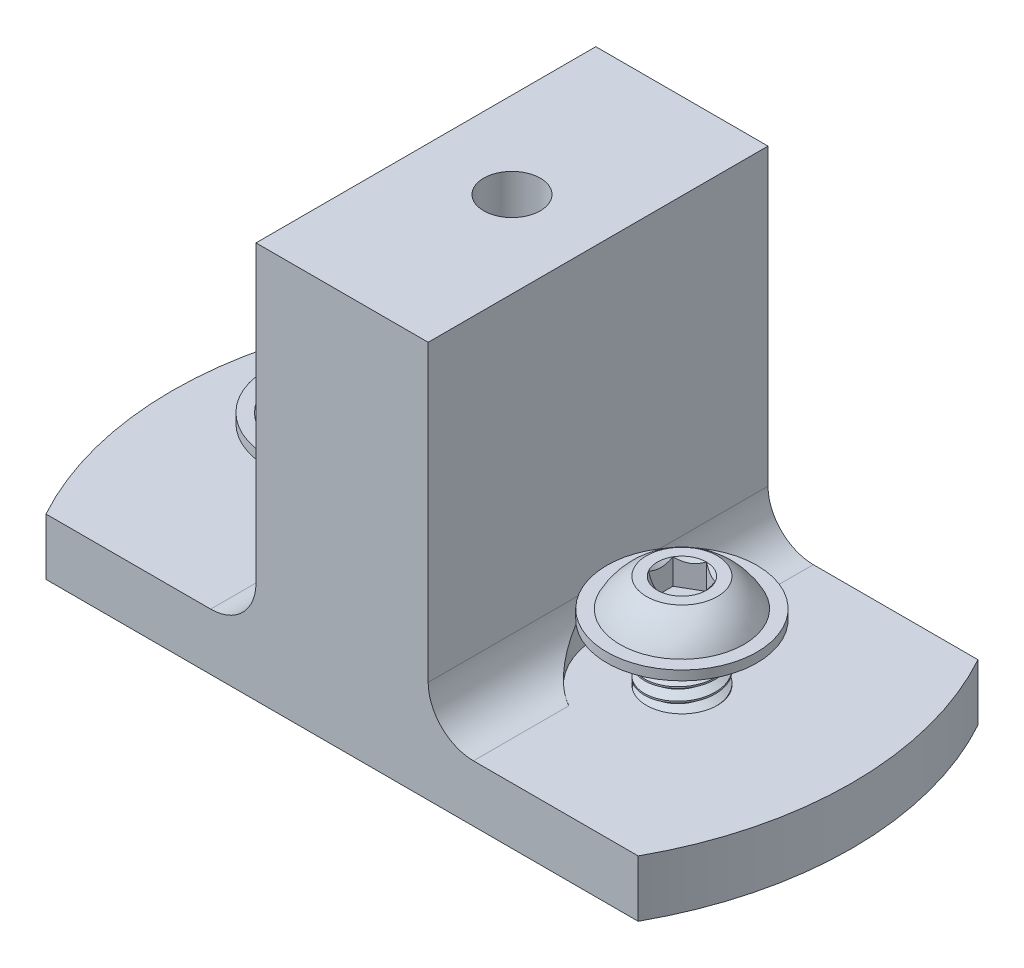
SolidWorks part; units mm, degrees
ref_plane "Front Plane" through (0, 0, 0) normal (0, 0, 1) x (1, 0, 0)
ref_plane "Top Plane" through (0, 0, 0) normal (0, 1, 0) x (1, 0, 0)
ref_plane "Right Plane" through (0, 0, 0) normal (1, 0, 0) x (0, 0, -1)
sketch "Sketch1" plane through (0, 0, 0) normal (0, 1, 0) x (1, 0, 0)
  line L0 (-19.05, 0) -> (19.05, 0) construction
  circle A0 centre (-19.05, 0) radius 3.9688
  point P3 (-23.0188, 0)
  point P4 (-15.0813, 0)
  dimension "D1" = 7.9375
  dimension "D2" = 38.1
extrude "Boss-Extrude1" add sketch "Sketch1" against normal blind 17.4625
sketch "Sketch2" plane through (0, -17.4625, 0) normal (0, -1, 0) x (1, 0, 0)
  circle A1 centre (-19.05, 0) radius 3.9688
  circle A2 centre (-19.05, 0) radius 3.9688
  point P0 (-19.05, -3.9688)
  dimension "D1" = 0
curve "Helix/Spiral1" pitch 1.4111 height 18.8736 turns 13.375
ref_plane "Plane1" through (-19.05, 0, 0) normal (1, 0, 0) x (0, 0, -1)
sketch "Sketch3" plane through (-19.05, 0, 0) normal (1, 0, 0) x (0, 0, -1)
  line L0 (4.1215, -17.3743) -> (2.8994, -18.0799) construction
  line L1 (2.8994, -18.0799) -> (4.1215, -18.7854) construction
  line L2 (4.1215, -18.7854) -> (4.1215, -17.3743) construction
  line L3 (3.0522, -17.9917) -> (3.0522, -18.1681) construction
  line L4 (3.9688, -17.4625) -> (3.9688, -18.6972) construction
  line L5 (2.8994, -18.0799) -> (3.0522, -18.0799) construction
  line L6 (3.9688, -18.0799) -> (4.1215, -18.0799) construction
  line L8 (2.8994, -18.0799) -> (-3.9688, -18.0799) construction
  line L9 (3.0522, -17.9917) -> (4.0451, -17.4184)
  line L10 (3.0522, -17.9917) -> (3.0522, -18.1681)
  line L11 (3.0522, -18.1681) -> (4.0451, -18.7413)
  line L12 (4.0451, -18.7413) -> (4.0451, -17.4184)
  line L14 (-3.9688, -18.0799) -> (-3.9688, -16.6687) construction
  line L15 (-3.9688, -16.6687) -> (-3.9688, -15.2576) construction
  line L16 (-3.9688, -15.2576) -> (-3.9687, -13.8465) construction
  line L17 (-3.9687, -13.8465) -> (-3.9688, -12.4354) construction
  line L18 (-3.9688, 0) -> (-3.9688, -17.4625) construction
  point P15 (4.0451, -18.0799)
  dimension "D1" = 1.4111
  dimension "D2" = 0.1764
sweep "Cut-Sweep1" cut profiles "Sketch3" path "Helix/Spiral1" align with end faces yes
sketch "Sketch4" plane through (0, -17.4625, 0) normal (0, -1, 0) x (1, 0, 0)
  circle A0 centre (-19.05, 0) radius 2.8994
extrude "Cut-Extrude1" cut sketch "Sketch4" against normal blind 1.4111 draft 45 flip side to cut
sketch "Sketch5" plane through (0, 0, 0) normal (0, 0, 1) x (1, 0, 0)
  line L0 (-19.05, 0) -> (-19.05, 4.2164)
  line L1 (-27.4701, 0) -> (-19.05, 0)
  line L2 (-19.05, 4.2164) -> (-23.0188, 4.2164)
  line L3 (-25.9969, 1.0541) -> (-27.4701, 1.0541)
  line L4 (-27.4701, 1.0541) -> (-27.4701, 0)
  line L5 (-19.05, 0) -> (-19.05, -17.4625) construction
  arc A0 (-23.0188, 4.2164) -> (-25.9969, 1.0541) centre (-19.05, -2.5047) ccw
  dimension "D1" = 4.2164
  dimension "D2" = 1.0541
  dimension "D3" = 16.8402
  dimension "D4" = 13.8938
revolve "Revolve1" add sketch "Sketch5" angle 360 mid plane about L0
sketch "Sketch6" plane through (0, 4.2164, 0) normal (0, 1, 0) x (1, 0, 0)
  line L1 (-19.05, 2.7496) -> (-21.4313, 1.3748)
  line L2 (-21.4313, 1.3748) -> (-21.4312, -1.3748)
  line L3 (-21.4312, -1.3748) -> (-19.05, -2.7496)
  line L4 (-19.05, -2.7496) -> (-16.6688, -1.3748)
  line L5 (-16.6688, -1.3748) -> (-16.6688, 1.3748)
  line L6 (-16.6688, 1.3748) -> (-19.05, 2.7496)
  circle A0 centre (-19.05, 0) radius 2.3813 construction
  dimension "D1" = 4.7625
extrude "Cut-Extrude2" cut sketch "Sketch6" against normal blind 2.8575
sketch "Sketch7" plane through (0, 4.2164, 0) normal (0, 1, 0) x (1, 0, 0)
  circle A0 centre (-19.05, 0) radius 2.7496
extrude "Cut-Extrude3" cut sketch "Sketch7" against normal blind 2.8575 draft 45
move or copy body "Body-Move/Copy1" bodies to move or copy 110 copy yes number of copies 1 translate (38.1, 0, 0)
sketch "Sketch8" plane through (0, 0, 0) normal (0, 1, 0) x (1, 0, 0)
  line L0 (-38.1, 0) -> (38.1, 0) construction
  line L2 (-33.1956, 19.05) -> (33.1956, 19.05)
  line L3 (-33.1956, -19.05) -> (33.1956, -19.05)
  line L4 (-38.1, 19.05) -> (38.1, 19.05) construction
  line L5 (-38.1, 19.05) -> (-38.1, -19.05) construction
  line L6 (-38.1, -19.05) -> (38.1, -19.05) construction
  line L7 (38.1, 19.05) -> (38.1, -19.05) construction
  arc A0 (-33.1956, 19.05) -> (-33.1956, -19.05) centre (1.3498, 0) ccw
  arc A1 (33.1956, 19.05) -> (33.1956, -19.05) centre (-1.3498, 0) cw
  circle A2 centre (19.05, 0) radius 3.9688
  circle A3 centre (-19.05, 0) radius 3.9688
  circle A4 centre (-19.05, 0) radius 3.9688
  dimension "D2" = 76.2
  dimension "D3" = 38.1
  dimension "D4" = 19.05
  dimension "D1" = 0
extrude "Boss-Extrude2" add sketch "Sketch8" against normal blind 6.35 from offset 6.35 separate body offset against normal yes
sketch "Sketch15" plane through (0, -6.35, 0) normal (0, 1, 0) x (1, 0, 0)
  line L0 (-10.6299, 0) -> (-10.6299, 19.05) construction
  line L1 (33.1956, 19.05) -> (-33.1956, 19.05) construction
  line L2 (10.6299, 0) -> (10.6299, 19.05) construction
  line L3 (0, 19.05) -> (-9.652, 19.05)
  line L4 (-9.652, 19.05) -> (-9.652, -19.05)
  line L5 (-33.1956, -19.05) -> (33.1956, -19.05) construction
  line L6 (0, 19.05) -> (9.652, 19.05)
  line L7 (9.652, 19.05) -> (9.652, -19.05)
  line L8 (9.652, -19.05) -> (-9.652, -19.05)
  circle A0 centre (-19.05, 0) radius 8.4201 construction
  circle A1 centre (19.05, 0) radius 8.4201 construction
  dimension "D1" = 19.304
extrude "Boss-Extrude7" add sketch "Sketch15" along normal blind 38.1
sketch "Sketch16" plane through (0, 31.75, 0) normal (0, 1, 0) x (1, 0, 0)
  circle A0 centre (0, 0) radius 3.175
extrude "Cut-Extrude5" cut sketch "Sketch16" against normal through all
sketch "Sketch9" plane through (0, -12.7, 0) normal (0, -1, 0) x (1, 0, 0)
  circle A0 centre (19.05, 0) radius 3.9688 construction
  circle A1 centre (-19.05, 0) radius 3.9688 construction
  circle A2 centre (-19.05, 0) radius 3.9688
  circle A3 centre (-19.05, 0) radius 4.5593
  circle A4 centre (19.05, 0) radius 3.9688
  circle A5 centre (19.05, 0) radius 4.5593
  dimension "D1" = 9.1186
sketch "SketchZ" plane through (0, 0, 0) normal (0, 0, 1) x (1, 0, 0)
  line L0 (-15.0813, -17.7271) -> (-15.0813, -16.316) construction
  line L2 (-19.05, -18.0799) -> (-19.05, -16.6687) construction
  line L4 (-15.0813, -17.7271) -> (-19.05, -17.7271) construction
  line L5 (-19.05, -13.8465) -> (-19.05, -12.4354) construction
  line L6 (-19.05, -17.3743) -> (-19.05, -18.0799) construction
sketch "Sketch19" plane through (0, -12.7, 0) normal (0, -1, 0) x (1, 0, 0)
  line L1 (0, 6.604) -> (-5.7192, 3.302)
  line L2 (-5.7192, 3.302) -> (-5.7192, -3.302)
  line L3 (-5.7192, -3.302) -> (0, -6.604)
  line L4 (0, -6.604) -> (5.7192, -3.302)
  line L5 (5.7192, -3.302) -> (5.7192, 3.302)
  line L6 (5.7192, 3.302) -> (0, 6.604)
  circle A0 centre (0, 0) radius 5.7192 construction
  dimension "D1" = 6.604
extrude "Cut-Extrude6" cut sketch "Sketch19" against normal blind 8.89
sketch "Sketch20" plane through (0, -6.35, 0) normal (0, 1, 0) x (1, 0, 0)
  circle A0 centre (19.05, 0) radius 9.398
  circle A1 centre (-19.05, 0) radius 9.398
fillet "Fillet1" radius 5.08 2 edges at (-9.652, -6.35, 0) (9.652, -6.35, 0)
extrude "Cut-Extrude7" cut sketch "Sketch20" along normal blind 12.7
equation "\"D3@Helix/Spiral1\" = \"D4@Helix/Spiral1\" + \"D1@Boss-Extrude1\""
equation "\"D1@Sketch3\" = \"D4@Helix/Spiral1\""
equation "\"D2@Sketch3\" = \"D1@Sketch3\" / 8"
equation "\"D1@Cut-Extrude1\" = \"D4@Helix/Spiral1\""
equation "\"D1@Cut-Extrude2\" = \"D1@Sketch6\" * 3/5"
equation "\"D1@Cut-Extrude3\" = \"D1@Cut-Extrude2\""
equation "\"D2@Sketch5\" = \"D1@Sketch5\" * 1/4"
